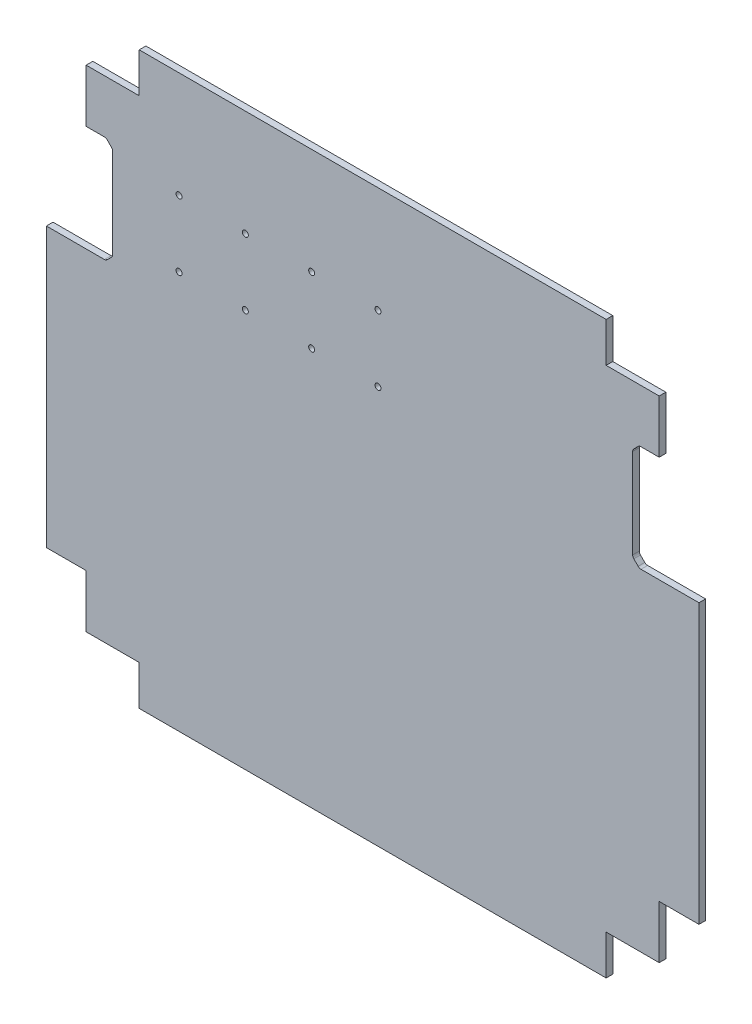
SolidWorks part; units mm, degrees
material "Acrílico (Impacto medio-alto)"
ref_plane "Alzado" through (0, 0, 0) normal (0, 0, 1) x (1, 0, 0)
ref_plane "Planta" through (0, 0, 0) normal (0, 1, 0) x (1, 0, 0)
ref_plane "Vista lateral" through (0, 0, 0) normal (1, 0, 0) x (0, 0, -1)
sketch "Croquis1" plane through (0, 0, 0) normal (0, 0, 1) x (1, 0, 0)
  line L0 (-246, 0) -> (246, 0)
  line L1 (0, 0) -> (0, 215) construction
  line L2 (-246, -145) -> (-246, 145)
  line L3 (-246, 145) -> (-216, 145)
  line L4 (-216, 145) -> (-216, 185)
  line L5 (-216, 185) -> (-176, 185)
  line L6 (-176, 185) -> (-176, 215)
  line L7 (-176, 215) -> (176, 215)
  line L8 (246, -145) -> (246, 145)
  line L9 (246, 145) -> (216, 145)
  line L10 (216, 145) -> (216, 185)
  line L11 (216, 185) -> (176, 185)
  line L12 (176, 185) -> (176, 215)
  line L13 (-246, -145) -> (-216, -145)
  line L14 (-216, -145) -> (-216, -185)
  line L15 (-216, -185) -> (-176, -185)
  line L16 (-176, -185) -> (-176, -215)
  line L17 (-176, -215) -> (176, -215)
  line L18 (176, -185) -> (176, -215)
  line L19 (216, -185) -> (176, -185)
  line L20 (216, -145) -> (216, -185)
  line L21 (246, -145) -> (216, -145)
  point P4 (0, 0)
  dimension "D1" = 492
  dimension "D2" = 145
  dimension "D3" = 216
  dimension "D4" = 176
  dimension "D5" = 30
  dimension "D6" = 40
extrude "Saliente-Extruir1" add sketch "Croquis1" along normal blind 5 contours L1 L0 L8 L9 L10 L11 L12 L7 | L0 L1 L7 L6 L5 L4 L3 L2 | L21 L8 L0 L2 L13 L14 L15 L16 L17 L18 L19 L20 region at (-116.66, 102.1915, 0) region at (0, -102.1915, 0) region at (116.66, 102.1915, 0)
sketch "Croquis3" plane through (0, 0, 5) normal (0, 0, 1) x (1, 0, 0)
  line L1 (-246, 145) -> (-196, 145)
  line L2 (-246, 145) -> (-246, 65)
  line L3 (-246, 65) -> (-196, 65)
  line L4 (-196, 145) -> (-196, 65)
  line L5 (246, 145) -> (196, 145)
  line L6 (246, 145) -> (246, 65)
  line L7 (246, 65) -> (196, 65)
  line L8 (196, 145) -> (196, 65)
  dimension "D1" = 50
  dimension "D2" = 80
  dimension "D3" = 50
  dimension "D4" = 80
extrude "Cortar-Extruir2" cut sketch "Croquis3" against normal blind 10 contours L2 L1 L4 L3 | L6 L5 L8 L7
chamfer "Chaflán1" distance 5 angle 45 4 edges at (-196, 65, 2.5) (-196, 145, 2.5) (196, 65, 2.5) (196, 145, 2.5)
fillet "Redondeo1" radius 3 8 edges at (196, 140, 2.5) (201, 145, 2.5) (201, 65, 2.5) (196, 70, 2.5) (-196, 140, 2.5) (-201, 145, 2.5) (-201, 65, 2.5) (-196, 70, 2.5)
sketch "Croquis4" plane through (0, 0, 5) normal (0, 0, 1) x (1, 0, 0)
  line L0 (-216, 145) -> (-216, 185) construction
  line L1 (-176, 215) -> (176, 215) construction
  circle A0 centre (-146, 135) radius 2.25
  circle A1 centre (-96, 135) radius 2.25
  circle A2 centre (-146, 85) radius 2.25
  circle A3 centre (-96, 85) radius 2.25
  circle A4 centre (-46, 135) radius 2.25
  circle A5 centre (-46, 85) radius 2.25
  circle A6 centre (4, 135) radius 2.25
  circle A7 centre (4, 85) radius 2.25
  point P20 (0, 0)
  point P21 (0, 0)
  point P22 (-70.9173, 132.2312)
  point P23 (-37.5869, 133.3817)
  point P24 (0, 0)
  point P25 (0, 0)
  point P26 (0, 0)
  point P27 (0, 0)
  point P28 (0, 0)
  dimension "D1" = 4.5
  dimension "D8" = 4.5
  dimension "D2" = 50
  dimension "D3" = 50
  dimension "D4" = 70
  dimension "D5" = 80
  dimension "D6" = 50
  dimension "D7" = 50
extrude "Cortar-Extruir3" cut sketch "Croquis4" against normal mid plane 10
